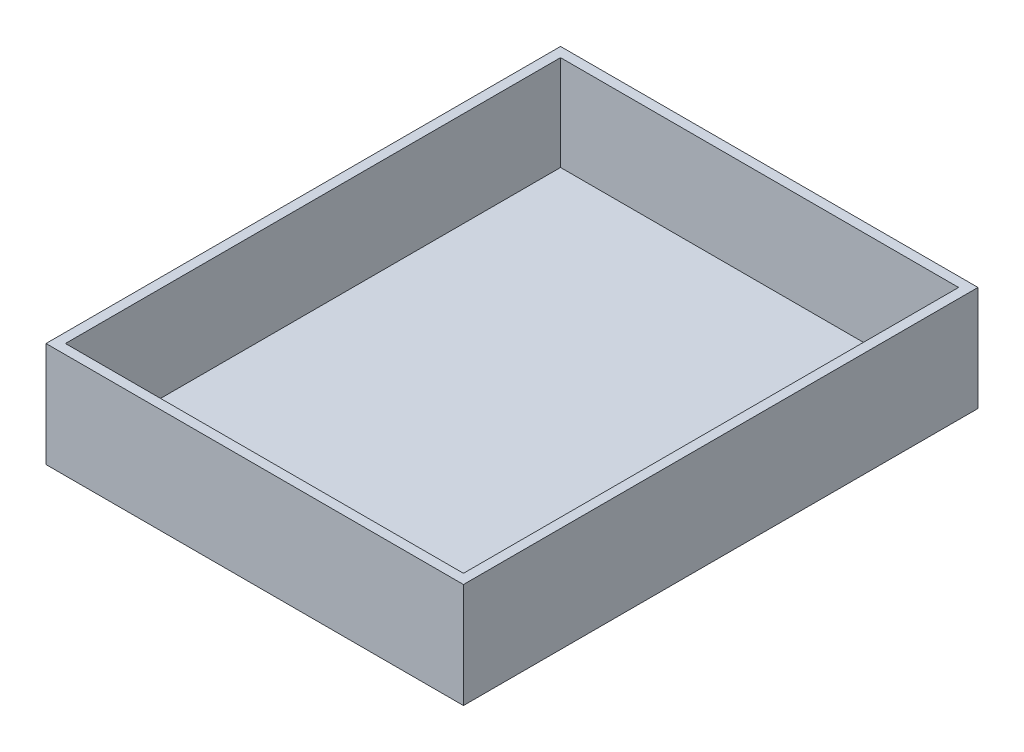
SolidWorks part; units mm, degrees
ref_plane "Front Plane" through (0, 0, 0) normal (0, 0, 1) x (1, 0, 0)
ref_plane "Top Plane" through (0, 0, 0) normal (0, 1, 0) x (1, 0, 0)
ref_plane "Right Plane" through (0, 0, 0) normal (1, 0, 0) x (0, 0, -1)
sketch "Base" plane through (0, 0, 0) normal (0, 1, 0) x (1, 0, 0)
  line L1 (-41, 51) -> (41, 51)
  line L2 (-41, 51) -> (-41, -51)
  line L3 (-41, -51) -> (41, -51)
  line L4 (41, 51) -> (41, -51)
  line L5 (-41, 51) -> (41, -51) construction
  line L6 (-41, -51) -> (41, 51) construction
  point P0 (0, 0)
  dimension "D1" = 82
  dimension "D2" = 102
extrude "Boss-Extrude1" add sketch "Base" along normal blind 19.6
shell "Shell2" thickness 2 removed face at (0, 19.6, 0) outward yes
